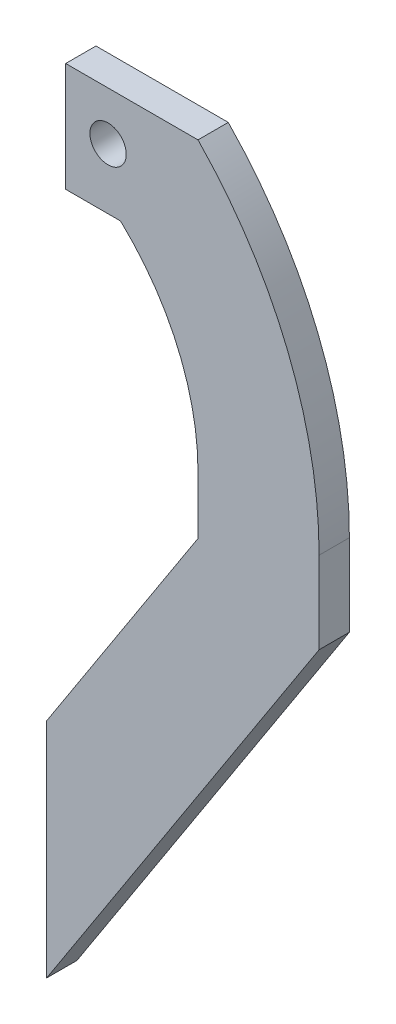
SolidWorks part; units mm, degrees
ref_plane "Front Plane" through (0, 0, 0) normal (0, 0, 1) x (1, 0, 0)
ref_plane "Top Plane" through (0, 0, 0) normal (0, 1, 0) x (1, 0, 0)
ref_plane "Right Plane" through (0, 0, 0) normal (1, 0, 0) x (0, 0, -1)
sketch "Sketch1" plane through (0, 0, 0) normal (0, 0, 1) x (1, 0, 0)
  line L0 (10.1476, -29.8732) -> (31.9976, -29.8732)
  line L2 (51.9976, -79.269) -> (51.9976, -92.7915)
  line L5 (6.9976, -162.2408) -> (6.9976, -125.4613)
  line L6 (6.9976, -125.4613) -> (31.9976, -86.8784)
  line L7 (31.9976, -86.8784) -> (31.9976, -77.316)
  line L9 (10.1476, -47.8732) -> (10.1476, -29.8732)
  line L10 (-3.1523, -37.8732) -> (17.1476, -37.8732) construction
  line L11 (6.9976, -37.8732) -> (6.9976, -171.5851) construction
  line L12 (51.9976, -92.7915) -> (6.9976, -162.2408)
  line L14 (10.1476, -47.8732) -> (19.2029, -47.8732)
  circle A1 centre (17.1476, -37.8732) radius 3
  arc A2 (31.9976, -77.316) -> (19.2029, -47.8732) centre (-8.2764, -77.316) ccw
  arc A3 (51.9976, -79.269) -> (31.9976, -29.8732) centre (-19.001, -79.269) ccw
  dimension "D2" = 8
  dimension "D1" = 10
  dimension "D3" = 7
  dimension "D4" = 25
  dimension "D5" = 20
  dimension "D6" = 20
extrude "Boss-Extrude1" add sketch "Sketch1" along normal blind 5
